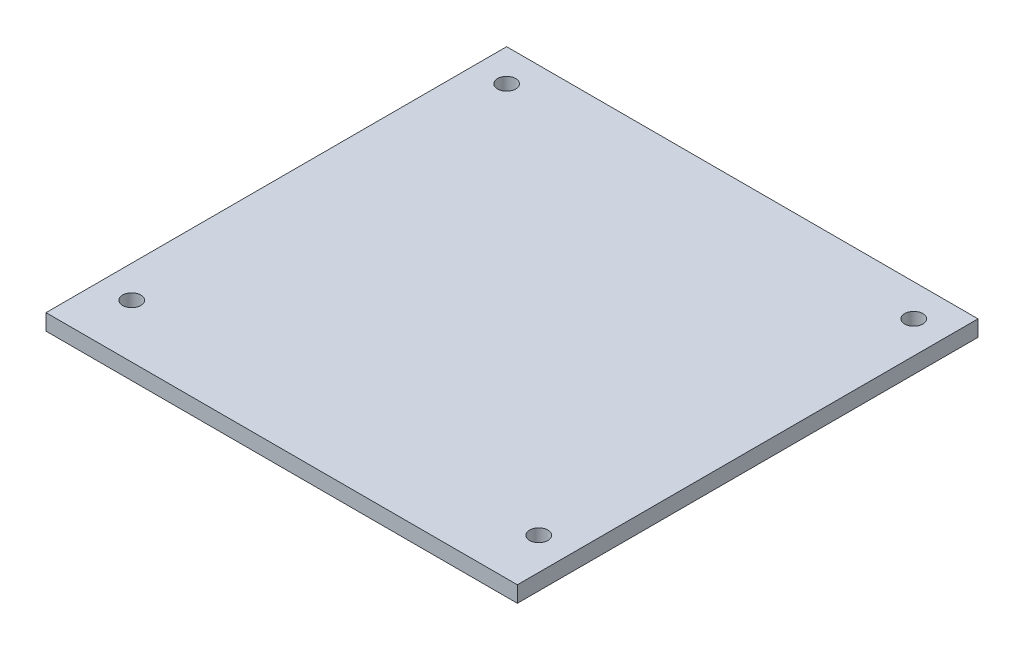
SolidWorks part; units mm, degrees
ref_plane "Спереди" through (0, 0, 0) normal (0, 0, 1) x (1, 0, 0)
ref_plane "Сверху" through (0, 0, 0) normal (0, 1, 0) x (1, 0, 0)
ref_plane "Справа" through (0, 0, 0) normal (1, 0, 0) x (0, 0, -1)
sketch "Sketch1" plane through (0, 0, 0) normal (0, 1, 0) x (1, 0, 0)
  line L1 (44, -41) -> (-44, -41)
  line L2 (44, -41) -> (44, 41)
  line L3 (44, 41) -> (-44, 41)
  line L4 (-44, -41) -> (-44, 41)
  line L5 (44, -41) -> (-44, 41) construction
  line L6 (44, 41) -> (-44, -41) construction
  point P0 (0, 0)
  dimension "D1" = 88
  dimension "D2" = 82
extrude "Boss-Extrude1" add sketch "Sketch1" along normal blind 3
sketch "Sketch2" plane through (0, 3, 0) normal (0, 1, 0) x (1, 0, 0)
  line L0 (-44, 41) -> (-44, -41) construction
  line L1 (38, -35) -> (-38, -35) construction
  line L2 (38, -35) -> (38, 35) construction
  line L3 (38, 35) -> (-38, 35) construction
  line L4 (-38, -35) -> (-38, 35) construction
  line L5 (38, -35) -> (-38, 35) construction
  line L6 (38, 35) -> (-38, -35) construction
  line L7 (44, 41) -> (-44, 41) construction
  circle A0 centre (-38, 35) radius 1.7
  circle A1 centre (38, 35) radius 1.7
  circle A2 centre (38, -35) radius 1.7
  circle A3 centre (-38, -35) radius 1.7
  point P0 (0, 0)
  dimension "D3" = 3.4
  dimension "D1" = 6
  dimension "D2" = 6
extrude "Cut-Extrude1" cut sketch "Sketch2" against normal through all
sketch "Sketch4" plane through (0, 0, 0) normal (0, -1, 0) x (1, 0, 0)
  line L0 (-44, -41) -> (-44, 41) construction
  line L1 (40.6, 37.6) -> (-40.6, 37.6)
  line L2 (40.6, 37.6) -> (40.6, -37.6)
  line L3 (40.6, -37.6) -> (-40.6, -37.6)
  line L4 (-40.6, 37.6) -> (-40.6, -37.6)
  line L5 (40.6, 37.6) -> (-40.6, -37.6) construction
  line L6 (40.6, -37.6) -> (-40.6, 37.6) construction
  line L7 (44, -41) -> (-44, -41) construction
  line L9 (37.6, 34.6) -> (-37.6, 34.6)
  line L10 (37.6, 34.6) -> (37.6, -34.6)
  line L11 (37.6, -34.6) -> (-37.6, -34.6)
  line L12 (-37.6, 34.6) -> (-37.6, -34.6)
  line L13 (37.6, 34.6) -> (-37.6, -34.6) construction
  line L14 (37.6, -34.6) -> (-37.6, 34.6) construction
  point P0 (0, 0)
  point P10 (0, 0)
  dimension "D1" = 3.4
  dimension "D2" = 3.4
  dimension "D3" = 3
  dimension "D4" = 3
extrude "Boss-Extrude2" add sketch "Sketch4" along normal blind 2
sketch "Sketch6" plane through (0, 3, 0) normal (0, 1, 0) x (1, 0, 0)
  line L0 (44, -41) -> (44, 41) construction
  circle A0 centre (-38, 35) radius 6
  circle A1 centre (-38, -35) radius 6
  circle A2 centre (38, -35) radius 6
  circle A3 centre (38, 35) radius 6
extrude "Cut-Extrude5" cut sketch "Sketch6" against normal through all from offset 3 offset against normal yes
sketch "Sketch7" plane through (0, 0, 41) normal (0, 0, 1) x (1, 0, 0)
  line L0 (-44, 3) -> (-44, 0)
  line L1 (-44, 0) -> (44, 0)
  line L2 (44, 0) -> (44, 3)
  line L3 (44, 3) -> (-44, 3)
extrude "Boss-Extrude3" add sketch "Sketch7" along normal blind 4
